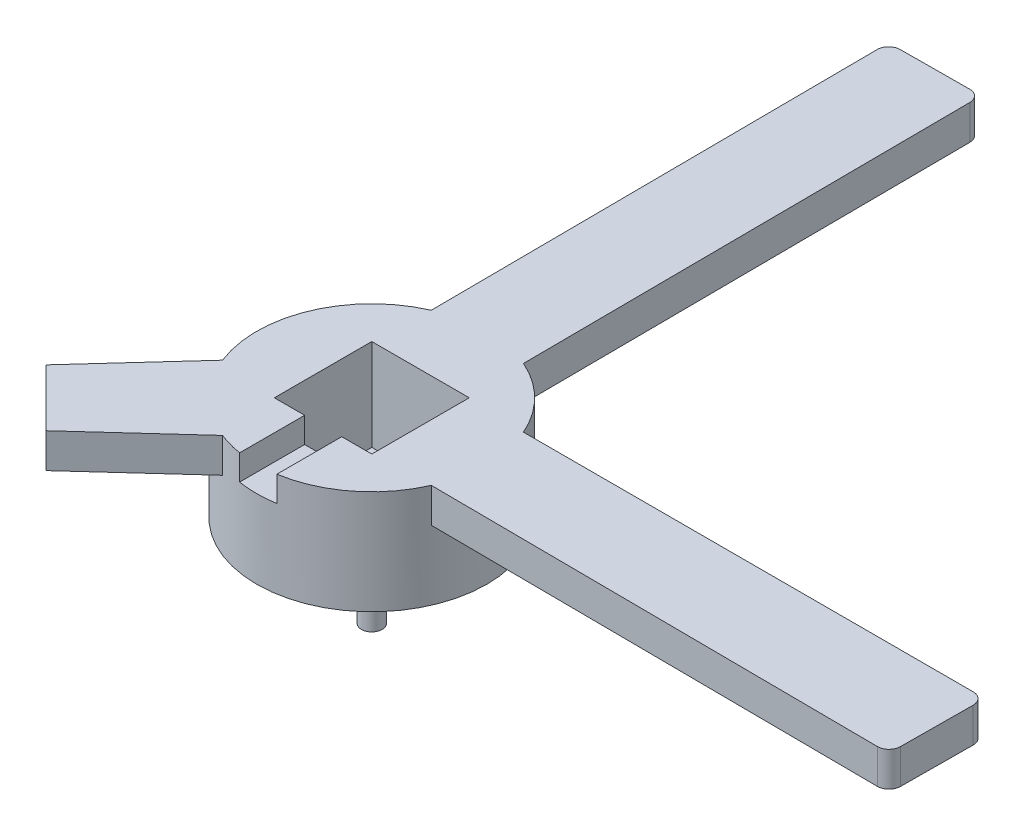
SolidWorks part; units mm, degrees
ref_plane "Front Plane" through (0, 0, 0) normal (0, 0, 1) x (1, 0, 0)
ref_plane "Top Plane" through (0, 0, 0) normal (0, 1, 0) x (1, 0, 0)
ref_plane "Right Plane" through (0, 0, 0) normal (1, 0, 0) x (0, 0, -1)
sketch "Sketch4" plane through (0, 39.8, 0) normal (0, 1, 0) x (1, 0, 0)
  circle A0 centre (-8.1132, -47.6273) radius 50
extrude "Boss-Extrude3" add sketch "Sketch4" against normal blind 45.1
sketch "Axis_Sketch" plane through (0, 0, 0) normal (0, -1, 0) x (1, 0, 0)
  line L1 (-8.1132, 47.6273) -> (-34.2032, 47.6273)
  line L2 (-8.1132, 47.6273) -> (-32.862, 22.8786)
  line L3 (-8.1132, 47.6273) -> (-32.862, 72.376)
  line L4 (-8.1132, 47.6273) -> (16.6355, 72.376)
  line L5 (-8.1132, 47.6273) -> (16.6355, 22.8786)
  line L6 (-8.1132, 47.6273) -> (-8.1132, 73.7173)
  line L7 (-8.1132, 47.6273) -> (17.9768, 47.6273)
  line L8 (-8.1132, 47.6273) -> (-8.1132, 21.5373)
  point P4 (-8.1132, 47.6273)
  point P11 (-8.1132, 47.6273)
  dimension "D1" = 26.09
  dimension "D2" = 4
  dimension "D3" = 35
  dimension "D4" = 4
  dimension "D5" = 45
sketch "Sketch16" plane through (0, -5.3, 0) normal (0, -1, 0) x (1, 0, 0)
  circle A0 centre (-8.1132, 21.5373) radius 4.5
  circle A1 centre (17.9768, 47.6273) radius 4.5
  circle A2 centre (-8.1132, 73.7173) radius 4.5
  circle A3 centre (-34.2032, 47.6273) radius 4.5
  circle A4 centre (-32.862, 22.8786) radius 4.5
  circle A5 centre (16.6355, 22.8786) radius 4.5
  circle A6 centre (16.6355, 72.376) radius 4.5
  circle A7 centre (-32.862, 72.376) radius 4.5
  dimension "D1" = 9
  dimension "D8" = 9
extrude "Boss-Extrude5" add sketch "Sketch16" along normal blind 15
sketch "Sketch5" plane through (0, 39.8, 0) normal (0, 1, 0) x (1, 0, 0)
  line L1 (-29.2632, -26.4773) -> (13.0368, -26.4773)
  line L2 (-29.2632, -26.4773) -> (-29.2632, -68.7773)
  line L3 (-29.2632, -68.7773) -> (13.0368, -68.7773)
  line L4 (13.0368, -26.4773) -> (13.0368, -68.7773)
  line L5 (-16.1132, -68.7773) -> (-0.1132, -68.7773)
extrude "Cut-Extrude1" cut sketch "Sketch5" against normal blind 39.8 contours L4 L1 L2 L3 region at (-8.1132, 39.8, 47.6273)
sketch "Sketch7" plane through (0, 39.8, 0) normal (0, 1, 0) x (1, 0, 0)
  line L0 (-29.2632, -68.7773) -> (13.0368, -68.7773) construction
  line L1 (-16.1132, -68.7773) -> (0, -68.7773)
  line L2 (-16.1132, -68.7773) -> (-16.1132, -104.2476)
  line L3 (-16.1132, -104.2476) -> (0, -104.2476)
  line L4 (0, -68.7773) -> (0, -104.2476)
  line L5 (-16.1132, -75.7773) -> (-16.1132, -68.7773) construction
extrude "Cut-Extrude3" cut sketch "Sketch7" against normal blind 11
sketch "Sketch8" plane through (0, 0, 0) normal (0, 1, 0) x (1, 0, 0)
  circle A0 centre (-8.1132, -47.6273) radius 11.15
  circle A1 centre (7.3868, -32.1273) radius 1.65
  circle A2 centre (7.3868, -63.1273) radius 1.65
  circle A3 centre (-23.6132, -63.1273) radius 1.65
  circle A4 centre (-23.6132, -32.1273) radius 1.65
  dimension "D1" = 3.3
  dimension "D2" = 22.3
extrude "Cut-Extrude4" cut sketch "Sketch8" against normal blind 5.3
sketch "Sketch9" plane through (0, -5.3, 0) normal (0, -1, 0) x (1, 0, 0)
  circle A0 centre (-23.6132, 32.1273) radius 2.9
  circle A1 centre (-23.6132, 63.1273) radius 2.9
  circle A2 centre (7.3868, 63.1273) radius 2.9
  circle A3 centre (7.3868, 32.1273) radius 2.9
  circle A4 centre (-23.6132, 32.1273) radius 1.65 construction
  circle A5 centre (7.3868, 32.1273) radius 1.65 construction
  circle A6 centre (7.3868, 63.1273) radius 1.65 construction
  circle A7 centre (-23.6132, 63.1273) radius 1.65 construction
  dimension "D1" = 5.8
extrude "Cut-Extrude5" cut sketch "Sketch9" against normal blind 3.2
sketch "Sketch11" plane through (0, 39.8, 0) normal (0, 1, 0) x (1, 0, 0)
  line L0 (-8.1132, -47.6273) -> (-58.1132, -47.6273) construction
  line L1 (-8.1132, -47.6273) -> (-43.4686, -82.9827) construction
  line L2 (-8.1132, -47.6273) -> (41.8868, -47.6273) construction
  line L3 (-8.1132, -47.6273) -> (-8.1132, 2.3727) construction
  line L8 (-8.1132, -1.8016) -> (-2.0252, -1.763)
  line L9 (-28.1132, -1.8016) -> (-29.3454, 192.9415)
  line L10 (11.8868, -1.8016) -> (10.653, 193.1945)
  line L11 (-24.3771, 197.973) -> (5.6215, 198.1628)
  line L13 (37.7125, -27.6273) -> (232.9621, -27.6273)
  line L14 (37.7125, -67.6273) -> (232.7078, -68.9914)
  line L15 (237.962, -32.6623) -> (237.7426, -64.0265)
  line L16 (-43.4686, -82.9827) -> (-78.8239, -118.338) construction
  line L17 (-91.1983, -105.9636) -> (-66.4495, -130.7124)
  line L18 (-54.6591, -65.8889) -> (-26.3748, -94.1732) construction
  line L19 (-54.6591, -65.8889) -> (-91.1983, -105.9636)
  line L20 (-26.3748, -94.1732) -> (-66.4495, -130.7124)
  arc A0 (0, -96.9647) -> (-16.1132, -96.9832) centre (-8.1132, -47.6273) ccw construction
  arc A1 (-54.6591, -65.8889) -> (-26.3748, -94.1732) centre (-8.1132, -47.6273) ccw
  arc A2 (37.7125, -27.6273) -> (37.7125, -67.6273) centre (-8.1132, -47.6273) cw
  arc A3 (-28.1132, -1.8016) -> (11.8868, -1.8016) centre (-8.1132, -47.6273) cw
  arc A4 (-29.3454, 192.9415) -> (-24.3771, 197.973) centre (-24.3455, 192.9731) cw
  arc A5 (10.653, 193.1945) -> (5.6215, 198.1628) centre (5.6531, 193.1629) ccw
  arc A6 (232.9621, -27.6273) -> (237.962, -32.6623) centre (232.9621, -32.6273) cw
  arc A7 (232.7078, -68.9914) -> (237.7426, -64.0265) centre (232.7427, -63.9915) ccw
  point P37 (10.6214, 198.1944)
  point P42 (237.7076, -69.0264)
  arc M28 (0, -96.9647) -> (-16.1132, -96.9832) centre (-8.1132, -47.6273) ccw
  dimension "D5" = 40
  dimension "D7" = 40
  dimension "D11" = 5
  dimension "D12" = 5
  dimension "D13" = 5
  dimension "D14" = 5
  dimension "D17" = 89.237
  dimension "D1" = 45
  dimension "D2" = 180
  dimension "D3" = 270
  dimension "D4" = 50
  dimension "D6" = 40
  dimension "D8" = 50
  dimension "D9" = 200
  dimension "D10" = 35
extrude "Boss-Extrude4" add sketch "Sketch11" against normal blind 15 contours L10 A5 L11 A4 L9 M28 | L14 A7 L15 A6 L13 M28 | A1 L20 L17 L19 region at (139.6086, 39.8, 47.9789) region at (-8.7494, 39.8, -99.4)
ref_axis "Planetary_Gear_Axis1" through (-34.2032, 0, 47.6273) along (0, -1, 0)
ref_axis "Planetary_Gear_Axis2" through (-8.1132, 0, 21.5373) along (0, -1, 0)
ref_axis "Planetary_Gear_Axis3" through (17.9768, 0, 47.6273) along (0, -1, 0)
ref_axis "Planetary_Gear_Axis4" through (-8.1132, 0, 73.7173) along (0, -1, 0)
ref_axis "Main_Support1" through (-32.862, 0, 22.8786) along (0, -1, 0)
ref_axis "Main_Support2" through (16.6355, 0, 22.8786) along (0, -1, 0)
ref_axis "Main_Support3" through (16.6355, 0, 72.376) along (0, -1, 0)
ref_axis "Main_Support4" through (-32.862, 0, 72.376) along (0, -1, 0)
ref_axis "Main_Axis" through (-8.1132, 0, 47.6273) along (0, -1, 0)
equation "\"D1@Boss-Extrude3\"=39.8+5.3"
